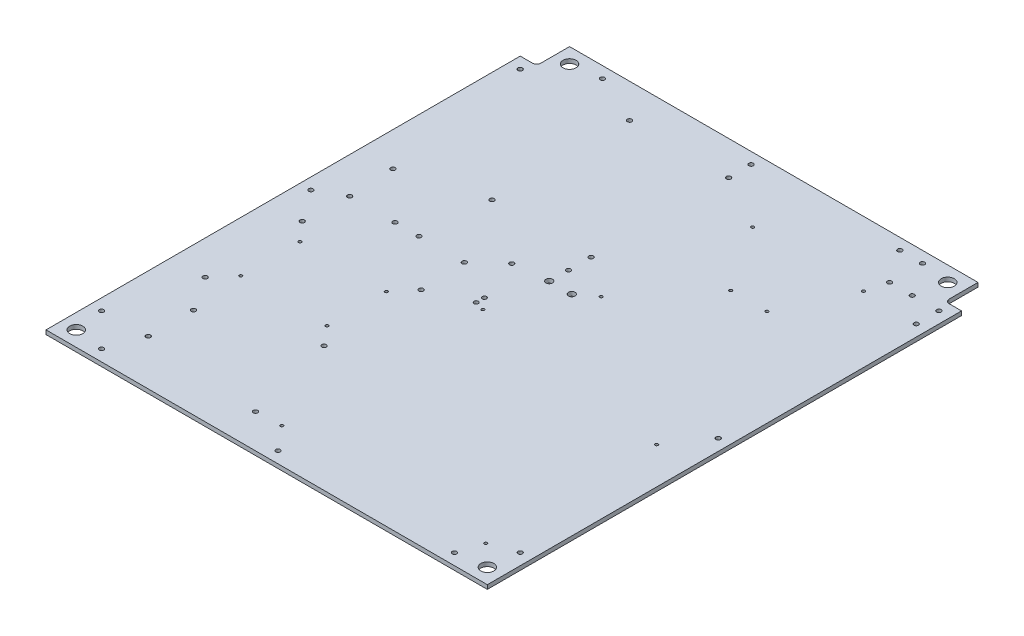
SolidWorks part; units mm, degrees
ref_plane "Front" through (0, 0, 0) normal (0, 0, 1) x (1, 0, 0)
ref_plane "Top" through (0, 0, 0) normal (0, 1, 0) x (1, 0, 0)
ref_plane "Right" through (0, 0, 0) normal (1, 0, 0) x (0, 0, -1)
sketch "Sketch1" plane through (0, 0, 0) normal (0, 1, 0) x (1, 0, 0)
  line L1 (170.434, -195.834) -> (-170.434, -195.834)
  line L2 (170.434, -195.834) -> (170.434, 195.834)
  line L3 (170.434, 195.834) -> (-170.434, 195.834)
  line L4 (-170.434, -195.834) -> (-170.434, 195.834)
  line L5 (170.434, -195.834) -> (-170.434, 195.834) construction
  line L6 (170.434, 195.834) -> (-170.434, -195.834) construction
  point P0 (0, 0)
  dimension "D1" = 340.868
  dimension "D2" = 391.668
extrude "Boss-Extrude1" add sketch "Sketch1" along normal blind 3.175
sketch "Sketch2" plane through (0, 3.175, 0) normal (0, 1, 0) x (1, 0, 0)
  line L0 (170.434, 195.834) -> (-170.434, 195.834) construction
  line L1 (-170.434, 195.834) -> (-157.734, 195.834)
  line L2 (-170.434, 195.834) -> (-170.434, 170.434)
  line L3 (-170.434, 170.434) -> (-160.909, 170.434)
  line L4 (-157.734, 195.834) -> (-157.734, 173.609)
  line L5 (170.434, 195.834) -> (157.734, 195.834)
  line L6 (170.434, 195.834) -> (170.434, 170.434)
  line L7 (170.434, 170.434) -> (160.909, 170.434)
  line L8 (157.734, 195.834) -> (157.734, 173.609)
  arc A0 (-157.734, 173.609) -> (-160.909, 170.434) centre (-160.909, 173.609) cw
  arc A1 (157.734, 173.609) -> (160.909, 170.434) centre (160.909, 173.609) ccw
  dimension "D1" = 3.175
  dimension "D2" = 25.4
  dimension "D3" = 12.7
extrude "Cut-Extrude1" cut sketch "Sketch2" against normal blind 10
hole_wizard "3/8 Clearance Hole1" positions "Sketch3" profile "Sketch4" hole size "3/8" standard "ANSI Inch" end condition through all
sketch "Sketch3" plane through (0, 3.175, 0) normal (0, 1, 0) x (1, 0, 0)
  line L0 (158.75, -184.15) -> (0, -184.15) construction
  line L1 (0, -184.15) -> (-158.75, -184.15) construction
  line L2 (-158.75, -184.15) -> (-158.75, -12.7) construction
  line L3 (-158.75, -12.7) -> (-158.75, 158.75) construction
  line L4 (-158.75, 158.75) -> (158.75, 158.75) construction
  line L5 (158.75, 158.75) -> (158.75, -12.7) construction
  line L6 (158.75, -12.7) -> (158.75, -184.15) construction
  line L8 (146.05, 184.15) -> (0, 184.15) construction
  line L9 (0, 184.15) -> (-146.05, 184.15) construction
  line L10 (-146.05, 184.15) -> (-157.734, 195.834) construction
  line L12 (157.734, 195.834) -> (146.05, 184.15) construction
  line L14 (-158.75, 158.75) -> (-170.434, 170.434) construction
  line L16 (-158.75, -184.15) -> (-170.434, -195.834) construction
  line L18 (158.75, 158.75) -> (170.434, 170.434) construction
  line L20 (158.75, -184.15) -> (170.434, -195.834) construction
  line L21 (158.75, -184.15) -> (158.75, -195.834) construction
  line L22 (-170.434, -195.834) -> (170.434, -195.834) construction
  line L24 (158.75, -184.15) -> (170.434, -184.15) construction
  line L25 (170.434, -195.834) -> (170.434, 170.434) construction
  point P0 (158.75, -184.15)
  point P2 (-158.75, -184.15)
  point P94 (-146.05, 184.15)
  point P96 (146.05, 184.15)
  dimension "D1" = 11.684
sketch "Sketch4" plane through (158.75, 3.175, 184.15) normal (1, 0, 0) x (0, 0, 1)
  line L0 (0, 0) -> (0, 3.175)
  line L1 (0, 3.175) -> (5.0419, 3.175)
  line L2 (5.0419, 3.175) -> (5.0419, 0)
  line L5 (5.0419, 0) -> (0, 0)
  line L11 (0, -6.35) -> (0, 107.95) construction
  dimension "Thru Hole Dia." = 10.0838
  dimension "Thru Hole Depth" = 3.175
hole_wizard "#4-40 Tapped Hole2" positions "Sketch9" profile "Sketch10" tap size "#4-40" standard "ANSI Inch" end condition through all
sketch "Sketch9" plane through (0, 3.175, 0) normal (0, 1, 0) x (1, 0, 0)
  circle A0 centre (33.725, 145.759) radius 1.6319 construction
  circle A1 centre (119.375, 145.759) radius 1.6319 construction
  circle A2 centre (142.14, -168.81) radius 1.95 construction
  circle A3 centre (-131.3281, -38.806) radius 2.7051 construction
  circle A4 centre (-64.6531, -38.806) radius 2.7051 construction
  circle A5 centre (-131.3281, -84.526) radius 2.7051 construction
  circle A6 centre (-64.6531, -84.526) radius 2.7051 construction
  point P4 (119.375, 145.759)
  point P6 (33.725, 145.759)
  point P20 (21.73, 40.754)
  point P23 (67.7, 94.894)
  point P26 (95.6, 94.894)
  point P30 (-15.34, -13.51)
  point P33 (142.14, -36.73)
  point P36 (142.14, -36.73)
  point P39 (-15.34, -168.81)
  point P42 (142.14, -168.81)
  point P48 (-64.6531, -38.806)
  point P50 (-64.6531, -84.526)
  point P52 (-131.3281, -38.806)
  point P54 (-131.3281, -84.526)
cosmetic thread "Hole Thread17" parameters "D2"=2.8448
cosmetic thread "Hole Thread18" parameters "D2"=2.8448
sketch "Sketch10" plane through (119.375, 3.175, -145.759) normal (1, 0, 0) x (0, 0, 1)
  line L0 (0, 0) -> (0, 3.175)
  line L1 (0, 3.175) -> (1.1303, 3.175)
  line L2 (1.1303, 3.175) -> (1.1303, 0)
  line L5 (1.1303, 0) -> (0, 0)
  line L11 (0, -6.35) -> (0, 107.95) construction
  dimension "Thru Tap Drill Dia." = 2.2606
  dimension "Thru Tap Drill Depth" = 3.175
cosmetic thread "Hole Thread19" parameters "D2"=2.8448
cosmetic thread "Hole Thread20" parameters "D2"=2.8448
cosmetic thread "Hole Thread21" parameters "D2"=2.8448
cosmetic thread "Hole Thread22" parameters "D2"=2.8448
cosmetic thread "Hole Thread23" parameters "D2"=2.8448
cosmetic thread "Hole Thread24" parameters "D2"=2.8448
cosmetic thread "Hole Thread25" parameters "D2"=2.8448
cosmetic thread "Hole Thread26" parameters "D2"=2.8448
cosmetic thread "Hole Thread27" parameters "D2"=2.8448
cosmetic thread "Hole Thread28" parameters "D2"=2.8448
cosmetic thread "Hole Thread29" parameters "D2"=2.8448
cosmetic thread "Hole Thread30" parameters "D2"=2.8448
hole_wizard "#8-32 Tapped Hole2" positions "Sketch13" profile "Sketch14" tap size "#8-32" standard "ANSI Inch" end condition through all
sketch "Sketch13" plane through (0, 3.175, 0) normal (0, 1, 0) x (1, 0, 0)
  line L34 (-161.684, 161.684) -> (-161.684, -161.684)
  line L36 (161.684, 144.184) -> (161.684, -161.684)
  line L38 (-123.584, 187.084) -> (106.084, 187.084)
  line L39 (106.084, 187.084) -> (123.584, 187.084)
  line L40 (123.584, 187.084) -> (123.584, 161.684)
  line L42 (123.584, 161.684) -> (141.084, 161.684)
  line L43 (141.084, 161.684) -> (161.684, 161.684)
  line L45 (161.684, 161.684) -> (161.684, 144.184)
  line L47 (-8.584, 187.084) -> (-8.584, 169.584)
  line L48 (-8.584, 169.584) -> (-8.584, 63.334)
  line L50 (-8.584, 63.334) -> (-8.584, 45.834)
  line L51 (-8.584, 45.834) -> (-144.184, 45.834)
  line L52 (-144.184, 45.834) -> (-161.684, 45.834)
  line L54 (-34.884, 45.834) -> (-34.884, 28.334)
  line L55 (-34.884, 28.334) -> (-34.884, -169.584)
  line L56 (-34.884, -169.584) -> (-34.884, -187.084)
  line L58 (-136.284, -187.084) -> (136.284, -187.084)
  line L60 (-161.684, -24.166) -> (-144.184, -24.166)
  line L61 (-144.184, -24.166) -> (-52.384, -24.166)
  line L62 (-52.384, -24.166) -> (-34.884, -24.166)
  line L64 (-161.684, -99.166) -> (-144.184, -99.166)
  line L65 (-144.184, -99.166) -> (-52.384, -99.166)
  line L66 (-52.384, -99.166) -> (-34.884, -99.166)
  line L68 (-161.684, 10.834) -> (-142.534, 10.834)
  line L69 (-142.534, 10.834) -> (-107.534, 10.834)
  line L70 (-107.534, 10.834) -> (-89.034, 10.834)
  line L71 (-89.034, 10.834) -> (-54.034, 10.834)
  line L72 (-54.034, 10.834) -> (-34.884, 10.834)
  line L74 (-85.134, 45.834) -> (-85.134, 63.334)
  line L75 (-85.134, 63.334) -> (-85.134, 169.584)
  line L76 (-85.134, 169.584) -> (-85.134, 187.084)
  line L78 (-170.434, 170.434) -> (-170.434, -195.834) construction
  line L79 (157.734, 195.834) -> (-157.734, 195.834) construction
  line L81 (170.434, -195.834) -> (170.434, 170.434) construction
  line L82 (-170.434, -195.834) -> (170.434, -195.834) construction
  line L83 (-170.434, 170.434) -> (-160.909, 170.434) construction
  line L84 (160.909, 170.434) -> (170.434, 170.434) construction
  line L85 (157.734, 195.834) -> (157.734, 173.609) construction
  line L86 (-157.734, 173.609) -> (-157.734, 195.834) construction
  line L87 (-76.384, 45.834) -> (-76.384, 10.834) construction
  line L88 (-76.384, 10.834) -> (-76.384, -24.166) construction
  line L90 (-161.684, 63.334) -> (-85.134, 63.334) construction
  line L92 (-85.134, 63.334) -> (-8.584, 63.334) construction
  line L93 (-126.684, -99.166) -> (-126.684, -125.625)
  line L94 (-126.684, -125.625) -> (-126.684, -160.625)
  line L95 (-126.684, -160.625) -> (-126.684, -187.084)
  point P146 (-161.684, -161.684)
  point P148 (-161.684, 0)
  point P150 (-161.684, 161.684)
  point P152 (-144.184, 45.834)
  point P154 (-8.584, 45.834)
  point P156 (-144.184, -24.166)
  point P158 (-52.384, -24.166)
  point P160 (-144.184, -99.166)
  point P162 (-52.384, -99.166)
  point P164 (-34.884, 28.334)
  point P166 (-34.884, -169.584)
  point P168 (-136.284, -187.084)
  point P170 (0, -187.084)
  point P172 (136.284, -187.084)
  point P174 (161.684, -161.684)
  point P176 (161.684, -8.75)
  point P178 (161.684, 144.184)
  point P180 (141.084, 161.684)
  point P182 (161.684, 161.684)
  point P184 (123.584, 161.684)
  point P186 (123.584, 187.084)
  point P188 (106.084, 187.084)
  point P190 (-123.584, 187.084)
  point P192 (-8.75, 187.084)
  point P194 (-8.584, 169.584)
  point P196 (-8.584, 63.334)
  point P198 (-142.534, 10.834)
  point P200 (-107.534, 10.834)
  point P202 (-89.034, 10.834)
  point P204 (-54.034, 10.834)
  point P206 (-85.134, 63.334)
  point P208 (-85.134, 169.584)
  point P345 (-126.684, -125.625)
  point P347 (-126.684, -160.625)
  dimension "D1" = 8.75
  dimension "D2" = 8.75
  dimension "D3" = 8.75
  dimension "D4" = 8.75
  dimension "D5" = 34.15
  dimension "D6" = 8.75
  dimension "D7" = 8.75
  dimension "D8" = 17.5
  dimension "D9" = 34.15
  dimension "D10" = 17.5
  dimension "D11" = 17.5
  dimension "D12" = 34.15
  dimension "D13" = 34.15
  dimension "D14" = 34.15
  dimension "D15" = 34.15
  dimension "D16" = 17.5
  dimension "D17" = 17.5
  dimension "D18" = 17.5
  dimension "D19" = 17.5
  dimension "D20" = 17.5
  dimension "D21" = 17.5
  dimension "D22" = 17.5
  dimension "D23" = 17.5
  dimension "D24" = 150
  dimension "D25" = 161.85
  dimension "D26" = 135.55
  dimension "D27" = 70
  dimension "D28" = 75
  dimension "D29" = 35
  dimension "D30" = 35
  dimension "D31" = 53.5
  dimension "D32" = 35
  dimension "D33" = 35
sketch "Sketch14" plane through (-161.684, 3.175, 161.684) normal (1, 0, 0) x (0, 0, 1)
  line L0 (0, 0) -> (0, 3.175)
  line L1 (0, 3.175) -> (1.7272, 3.175)
  line L2 (1.7272, 3.175) -> (1.7272, 0)
  line L5 (1.7272, 0) -> (0, 0)
  line L11 (0, -6.35) -> (0, 107.95) construction
  dimension "Thread Major Dia." = 3.4544
  dimension "Thru Tap Drill Depth" = 3.175
hole_wizard "#4 Clearance Hole1" positions "Sketch15" profile "Sketch16" hole size "#4" standard "ANSI Inch"
sketch "Sketch15" plane through (0, 3.175, 0) normal (0, 1, 0) x (1, 0, 0)
  point P0 (-22.642, -11.3606)
  point P3 (-22.642, -5.0106)
  point P6 (0, 0)
sketch "Sketch16" plane through (-22.642, 3.175, 11.3606) normal (1, 0, 0) x (0, 0, 1)
  line L0 (0, 0) -> (0, 8.9906)
  line L1 (0, 8.9906) -> (1.6319, 8.01)
  line L2 (1.6319, 8.01) -> (1.6319, 0)
  line L5 (1.6319, 0) -> (0, 0)
  line L10 (0, 8.9906) -> (-1.632, 8.01) construction
  line L11 (0, -6.35) -> (0, 107.95) construction
  dimension "Hole Dia." = 3.2639
  dimension "Hole Depth" = 8.01
  dimension "Drill Angle" = 118
hole_wizard "#10 Clearance Hole1" positions "Sketch17" profile "Sketch18" hole size "#10" standard "ANSI Inch" end condition through all
sketch "Sketch17" plane through (0, 0, 0) normal (0, -1, 0) x (-1, 0, 0)
  circle A0 centre (-8.7376, 31.1216) radius 2.032 construction
  circle A1 centre (8.7376, 31.1216) radius 2.032 construction
  point P0 (8.7376, 31.1216)
  point P2 (-8.7376, 31.1216)
sketch "Sketch18" plane through (-8.7376, 0, -31.1216) normal (1, 0, 0) x (0, 0, -1)
  line L0 (0, 0) -> (0, 3.175)
  line L1 (0, 3.175) -> (2.5527, 3.175)
  line L2 (2.5527, 3.175) -> (2.5527, 0)
  line L5 (2.5527, 0) -> (0, 0)
  line L11 (0, -6.35) -> (0, 107.95) construction
  dimension "Thru Hole Dia." = 5.1054
  dimension "Thru Hole Depth" = 3.175
